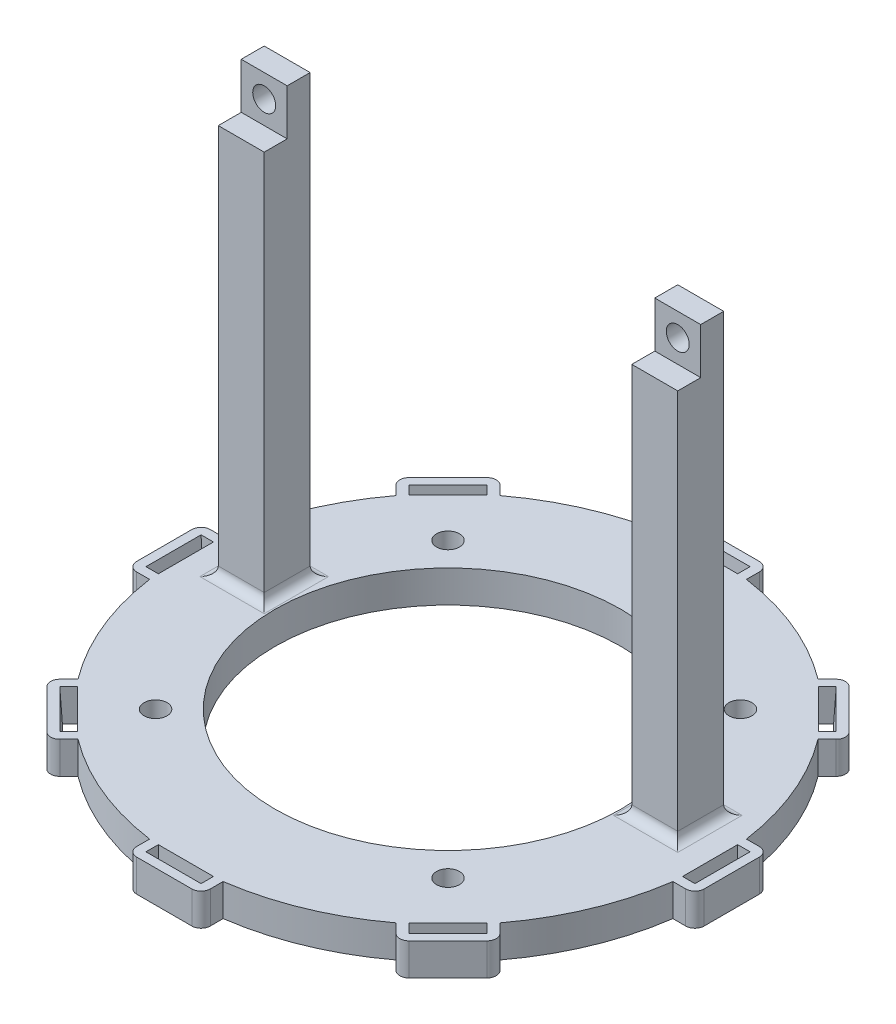
SolidWorks part; units mm, degrees
note: The reader was unsure of these and kept them because the rebuilt part matched: shared geometry of "Sketch9<2>".
ref_plane "Front Plane" through (0, 0, 0) normal (0, 0, 1) x (1, 0, 0)
ref_plane "Top Plane" through (0, 0, 0) normal (0, 1, 0) x (1, 0, 0)
ref_plane "Right Plane" through (0, 0, 0) normal (1, 0, 0) x (0, 0, -1)
sketch "Sketch1" plane through (0, 0, 0) normal (0, 1, 0) x (1, 0, 0)
  line L0 (-8, 56.9408) -> (-8, 59.7408)
  line L1 (0, 57.5) -> (0, -57.5) construction
  line L2 (8, 56.9408) -> (8, 59.7408)
  line L3 (-6, 61.7408) -> (6, 61.7408)
  line L4 (39.4147, 47.8999) -> (47.8999, 39.4147)
  line L9 (34.6063, 45.9201) -> (36.5862, 47.8999)
  line L10 (45.9201, 34.6063) -> (47.8999, 36.5862)
  line L15 (61.7408, 6) -> (61.7408, -6)
  line L16 (56.9408, 8) -> (59.7408, 8)
  line L17 (56.9408, -8) -> (59.7408, -8)
  line L22 (47.8999, -39.4147) -> (39.4147, -47.8999)
  line L23 (45.9201, -34.6063) -> (47.8999, -36.5862)
  line L24 (34.6063, -45.9201) -> (36.5862, -47.8999)
  line L29 (6, -61.7408) -> (-6, -61.7408)
  line L30 (8, -56.9408) -> (8, -59.7408)
  line L31 (-8, -56.9408) -> (-8, -59.7408)
  line L36 (-39.4147, -47.8999) -> (-47.8999, -39.4147)
  line L37 (-34.6063, -45.9201) -> (-36.5862, -47.8999)
  line L38 (-45.9201, -34.6063) -> (-47.8999, -36.5862)
  line L43 (-61.7408, -6) -> (-61.7408, 6)
  line L44 (-56.9408, -8) -> (-59.7408, -8)
  line L45 (-56.9408, 8) -> (-59.7408, 8)
  line L50 (-47.8999, 39.4147) -> (-39.4147, 47.8999)
  line L51 (-45.9201, 34.6063) -> (-47.8999, 36.5862)
  line L52 (-34.6063, 45.9201) -> (-36.5862, 47.8999)
  arc A0 (-8, 56.9408) -> (-34.6063, 45.9201) centre (0, 0) ccw
  arc A1 (6, 61.7408) -> (8, 59.7408) centre (6, 59.7408) cw
  arc A2 (-6, 61.7408) -> (-8, 59.7408) centre (-6, 59.7408) ccw
  arc A3 (39.4147, 47.8999) -> (36.5862, 47.8999) centre (38.0005, 46.4857) ccw
  arc A4 (47.8999, 39.4147) -> (47.8999, 36.5862) centre (46.4857, 38.0005) cw
  arc A5 (61.7408, 6) -> (59.7408, 8) centre (59.7408, 6) ccw
  arc A6 (61.7408, -6) -> (59.7408, -8) centre (59.7408, -6) cw
  arc A7 (47.8999, -39.4147) -> (47.8999, -36.5862) centre (46.4857, -38.0005) ccw
  arc A8 (39.4147, -47.8999) -> (36.5862, -47.8999) centre (38.0005, -46.4857) cw
  arc A9 (6, -61.7408) -> (8, -59.7408) centre (6, -59.7408) ccw
  arc A10 (-6, -61.7408) -> (-8, -59.7408) centre (-6, -59.7408) cw
  arc A11 (-39.4147, -47.8999) -> (-36.5862, -47.8999) centre (-38.0005, -46.4857) ccw
  arc A12 (-47.8999, -39.4147) -> (-47.8999, -36.5862) centre (-46.4857, -38.0005) cw
  arc A13 (-61.7408, -6) -> (-59.7408, -8) centre (-59.7408, -6) ccw
  arc A14 (-61.7408, 6) -> (-59.7408, 8) centre (-59.7408, 6) cw
  arc A15 (-47.8999, 39.4147) -> (-47.8999, 36.5862) centre (-46.4857, 38.0005) ccw
  arc A16 (-39.4147, 47.8999) -> (-36.5862, 47.8999) centre (-38.0005, 46.4857) cw
  arc A17 (-45.9201, 34.6063) -> (-56.9408, 8) centre (0, 0) ccw
  arc A18 (-56.9408, -8) -> (-45.9201, -34.6063) centre (0, 0) ccw
  arc A19 (34.6063, 45.9201) -> (8, 56.9408) centre (0, 0) ccw
  arc A20 (-34.6063, -45.9201) -> (-8, -56.9408) centre (0, 0) ccw
  arc A21 (8, -56.9408) -> (34.6063, -45.9201) centre (0, 0) ccw
  arc A22 (45.9201, -34.6063) -> (56.9408, -8) centre (0, 0) ccw
  arc A23 (56.9408, 8) -> (45.9201, 34.6063) centre (0, 0) ccw
  point P11 (8, 61.7408)
  point P14 (-8, 61.7408)
  point P17 (-8, 58.3408)
  point P98 (0, 0)
  dimension "D1" = 115
  dimension "D2" = 2
  dimension "D3" = 16
  dimension "D4" = 2.8
  dimension "D7" = 8
extrude "Boss-Extrude1" add sketch "Sketch1" along normal blind 7
sketch "Sketch3" plane through (0, 7, 0) normal (0, 1, 0) x (1, 0, 0)
  circle A0 centre (0, 0) radius 37.6637
extrude "Cut-Extrude1" cut sketch "Sketch3" against normal through all
sketch "Sketch5" plane through (0, 7, 0) normal (0, 1, 0) x (1, 0, 0)
  line L1 (-6, 59.7408) -> (6, 59.7408)
  line L2 (-6, 59.7408) -> (-6, 57.0408)
  line L3 (-6, 57.0408) -> (6, 57.0408)
  line L4 (6, 59.7408) -> (6, 57.0408)
  line L24 (8, 56.9408) -> (8, 59.7408)
  line L25 (6, 61.7408) -> (-6, 61.7408)
  line L26 (-8, 59.7408) -> (-8, 56.9408)
  line L27 (-34.6063, 45.9201) -> (-36.5862, 47.8999)
  line L28 (-39.4147, 47.8999) -> (-47.8999, 39.4147)
  line L29 (-47.8999, 36.5862) -> (-45.9201, 34.6063)
  line L30 (-56.9408, 8) -> (-59.7408, 8)
  line L31 (-61.7408, 6) -> (-61.7408, -6)
  line L32 (-59.7408, -8) -> (-56.9408, -8)
  line L33 (-45.9201, -34.6063) -> (-47.8999, -36.5862)
  line L34 (-47.8999, -39.4147) -> (-39.4147, -47.8999)
  line L35 (-36.5862, -47.8999) -> (-34.6063, -45.9201)
  line L36 (-8, -56.9408) -> (-8, -59.7408)
  line L37 (-6, -61.7408) -> (6, -61.7408)
  line L38 (8, -59.7408) -> (8, -56.9408)
  line L39 (34.6063, -45.9201) -> (36.5862, -47.8999)
  line L40 (39.4147, -47.8999) -> (47.8999, -39.4147)
  line L41 (47.8999, -36.5862) -> (45.9201, -34.6063)
  line L42 (56.9408, -8) -> (59.7408, -8)
  line L43 (61.7408, -6) -> (61.7408, 6)
  line L44 (59.7408, 8) -> (56.9408, 8)
  line L45 (45.9201, 34.6063) -> (47.8999, 36.5862)
  line L46 (47.8999, 39.4147) -> (39.4147, 47.8999)
  line L47 (36.5862, 47.8999) -> (34.6063, 45.9201)
  line L48 (8, 56.9408) -> (8, 59.7408)
  line L49 (6, 61.7408) -> (-6, 61.7408)
  line L50 (-8, 59.7408) -> (-8, 56.9408)
  line L51 (-34.6063, 45.9201) -> (-36.5862, 47.8999)
  line L52 (-39.4147, 47.8999) -> (-47.8999, 39.4147)
  line L53 (-47.8999, 36.5862) -> (-45.9201, 34.6063)
  line L54 (-56.9408, 8) -> (-59.7408, 8)
  line L55 (-61.7408, 6) -> (-61.7408, -6)
  line L56 (-59.7408, -8) -> (-56.9408, -8)
  line L57 (-45.9201, -34.6063) -> (-47.8999, -36.5862)
  line L58 (-47.8999, -39.4147) -> (-39.4147, -47.8999)
  line L59 (-36.5862, -47.8999) -> (-34.6063, -45.9201)
  line L60 (-8, -56.9408) -> (-8, -59.7408)
  line L61 (-6, -61.7408) -> (6, -61.7408)
  line L62 (8, -59.7408) -> (8, -56.9408)
  line L63 (34.6063, -45.9201) -> (36.5862, -47.8999)
  line L64 (39.4147, -47.8999) -> (47.8999, -39.4147)
  line L65 (47.8999, -36.5862) -> (45.9201, -34.6063)
  line L66 (56.9408, -8) -> (59.7408, -8)
  line L67 (61.7408, -6) -> (61.7408, 6)
  line L68 (59.7408, 8) -> (56.9408, 8)
  line L69 (45.9201, 34.6063) -> (47.8999, 36.5862)
  line L70 (47.8999, 39.4147) -> (39.4147, 47.8999)
  line L71 (36.5862, 47.8999) -> (34.6063, 45.9201)
  arc A24 (34.6063, 45.9201) -> (8, 56.9408) centre (0, 0) ccw
  arc A25 (8, 59.7408) -> (6, 61.7408) centre (6, 59.7408) ccw
  arc A26 (-6, 61.7408) -> (-8, 59.7408) centre (-6, 59.7408) ccw
  arc A27 (-8, 56.9408) -> (-34.6063, 45.9201) centre (0, 0) ccw
  arc A28 (-36.5862, 47.8999) -> (-39.4147, 47.8999) centre (-38.0005, 46.4857) ccw
  arc A29 (-47.8999, 39.4147) -> (-47.8999, 36.5862) centre (-46.4857, 38.0005) ccw
  arc A30 (-45.9201, 34.6063) -> (-56.9408, 8) centre (0, 0) ccw
  arc A31 (-59.7408, 8) -> (-61.7408, 6) centre (-59.7408, 6) ccw
  arc A32 (-61.7408, -6) -> (-59.7408, -8) centre (-59.7408, -6) ccw
  arc A33 (-56.9408, -8) -> (-45.9201, -34.6063) centre (0, 0) ccw
  arc A34 (-47.8999, -36.5862) -> (-47.8999, -39.4147) centre (-46.4857, -38.0005) ccw
  arc A35 (-39.4147, -47.8999) -> (-36.5862, -47.8999) centre (-38.0005, -46.4857) ccw
  arc A36 (-34.6063, -45.9201) -> (-8, -56.9408) centre (0, 0) ccw
  arc A37 (-8, -59.7408) -> (-6, -61.7408) centre (-6, -59.7408) ccw
  arc A38 (6, -61.7408) -> (8, -59.7408) centre (6, -59.7408) ccw
  arc A39 (8, -56.9408) -> (34.6063, -45.9201) centre (0, 0) ccw
  arc A40 (36.5862, -47.8999) -> (39.4147, -47.8999) centre (38.0005, -46.4857) ccw
  arc A41 (47.8999, -39.4147) -> (47.8999, -36.5862) centre (46.4857, -38.0005) ccw
  arc A42 (45.9201, -34.6063) -> (56.9408, -8) centre (0, 0) ccw
  arc A43 (59.7408, -8) -> (61.7408, -6) centre (59.7408, -6) ccw
  arc A44 (61.7408, 6) -> (59.7408, 8) centre (59.7408, 6) ccw
  arc A45 (56.9408, 8) -> (45.9201, 34.6063) centre (0, 0) ccw
  arc A46 (47.8999, 36.5862) -> (47.8999, 39.4147) centre (46.4857, 38.0005) ccw
  arc A47 (39.4147, 47.8999) -> (36.5862, 47.8999) centre (38.0005, 46.4857) ccw
  arc A48 (34.6063, 45.9201) -> (8, 56.9408) centre (0, 0) ccw
  arc A49 (8, 59.7408) -> (6, 61.7408) centre (6, 59.7408) ccw
  arc A50 (-6, 61.7408) -> (-8, 59.7408) centre (-6, 59.7408) ccw
  arc A51 (-8, 56.9408) -> (-34.6063, 45.9201) centre (0, 0) ccw
  arc A52 (-36.5862, 47.8999) -> (-39.4147, 47.8999) centre (-38.0005, 46.4857) ccw
  arc A53 (-47.8999, 39.4147) -> (-47.8999, 36.5862) centre (-46.4857, 38.0005) ccw
  arc A54 (-45.9201, 34.6063) -> (-56.9408, 8) centre (0, 0) ccw
  arc A55 (-59.7408, 8) -> (-61.7408, 6) centre (-59.7408, 6) ccw
  arc A56 (-61.7408, -6) -> (-59.7408, -8) centre (-59.7408, -6) ccw
  arc A57 (-56.9408, -8) -> (-45.9201, -34.6063) centre (0, 0) ccw
  arc A58 (-47.8999, -36.5862) -> (-47.8999, -39.4147) centre (-46.4857, -38.0005) ccw
  arc A59 (-39.4147, -47.8999) -> (-36.5862, -47.8999) centre (-38.0005, -46.4857) ccw
  arc A60 (-34.6063, -45.9201) -> (-8, -56.9408) centre (0, 0) ccw
  arc A61 (-8, -59.7408) -> (-6, -61.7408) centre (-6, -59.7408) ccw
  arc A62 (6, -61.7408) -> (8, -59.7408) centre (6, -59.7408) ccw
  arc A63 (8, -56.9408) -> (34.6063, -45.9201) centre (0, 0) ccw
  arc A64 (36.5862, -47.8999) -> (39.4147, -47.8999) centre (38.0005, -46.4857) ccw
  arc A65 (47.8999, -39.4147) -> (47.8999, -36.5862) centre (46.4857, -38.0005) ccw
  arc A66 (45.9201, -34.6063) -> (56.9408, -8) centre (0, 0) ccw
  arc A67 (59.7408, -8) -> (61.7408, -6) centre (59.7408, -6) ccw
  arc A68 (61.7408, 6) -> (59.7408, 8) centre (59.7408, 6) ccw
  arc A69 (56.9408, 8) -> (45.9201, 34.6063) centre (0, 0) ccw
  arc A70 (47.8999, 36.5862) -> (47.8999, 39.4147) centre (46.4857, 38.0005) ccw
  arc A71 (39.4147, 47.8999) -> (36.5862, 47.8999) centre (38.0005, 46.4857) ccw
  dimension "D2" = 12
  dimension "D3" = 2.7
  dimension "D1" = 0
sketch "Sketch7" plane through (0, 0, 0) normal (0, -1, 0) x (1, 0, 0)
  line L0 (6, -59.7408) -> (6, -57.0408) construction
  line L1 (-6, -57.0408) -> (6, -57.0408)
  line L2 (-6, -57.0408) -> (-6, -59.3408)
  line L3 (-6, -59.3408) -> (6, -59.3408)
  line L4 (6, -57.0408) -> (6, -59.3408)
  dimension "D1" = 2.3
loft "Cut-Loft1" cut profiles "Sketch7" section "Sketch7" section "Sketch5" connector at (6, 0, -59.3408) connector at (6, 7, -59.7408)
pattern_circular "CirPattern1" count 8 every 45 about axis through (0, 0, 0) along (0, 1, 0) of "Cut-Loft1"
sketch "Sketch8" plane through (0, 7, 0) normal (0, 1, 0) x (1, 0, 0)
  line L1 (50, 10) -> (40, 10)
  line L2 (50, 10) -> (50, 0)
  line L3 (50, 0) -> (40, 0)
  line L4 (40, 10) -> (40, 0)
  line L5 (0, -3.8501) -> (0, 3.8501) construction
  line L6 (-40, 10) -> (-40, 0)
  line L7 (-50, 0) -> (-40, 0)
  line L8 (-50, 10) -> (-50, 0)
  line L9 (-50, 10) -> (-40, 10)
  dimension "D1" = 10
  dimension "D2" = 40
extrude "Boss-Extrude2" add sketch "Sketch8" along normal blind 95
sketch "Sketch9" plane through (0, 0, 0) normal (0, 0, 1) x (1, 0, 0)
  line L0 (-50, 102) -> (-50, 7) construction
  line L1 (-40, 102) -> (-50, 102)
  line L2 (-40, 102) -> (-40, 92)
  line L3 (-40, 92) -> (-50, 92)
  line L4 (-50, 102) -> (-50, 92)
  line L10 (-50, 92) -> (-40, 102) construction
  circle A0 centre (-45, 97) radius 2.5
  dimension "D2" = 5
  dimension "D1" = 10
extrude "Cut-Extrude2" cut sketch "Sketch9" against normal blind 5
extrude "Cut-Extrude3" cut sketch "Sketch9<2>" against normal through all contours A0 L10 | L10 A0
sketch "Sketch9<2>" plane through (0, 0, 0) normal (0, 0, 1) x (1, 0, 0) same geometry as "Sketch9"
mirror "Mirror1" about plane through (0, 0, 0) normal (1, 0, 0) of "Cut-Extrude3", "Cut-Extrude2"
sketch "Sketch11" plane through (0, 0, 0) normal (0, -1, 0) x (1, 0, 0)
  line L0 (0, 0) -> (-52.3062, 0) construction
  line L1 (0, 0) -> (-31.8198, -31.8198) construction
  circle A0 centre (-31.8198, -31.8198) radius 2.5
  dimension "D3" = 5
  dimension "D1" = 45
  dimension "D2" = 45
extrude "Cut-Extrude4" cut sketch "Sketch11" against normal through all
pattern_circular "CirPattern2" count 4 every 90 about axis through (0, 0, 0) along (0, 1, 0) of "Cut-Extrude4"
fillet "Fillet1" radius 2 8 edges at (50, 7, -5) (45, 7, -10) (40, 7, -5) (45, 7, 0) (-50, 7, -5) (-45, 7, -10) (-45, 7, 0) (-40, 7, -5)
equation "\"85.00.00mm\"=8500"
